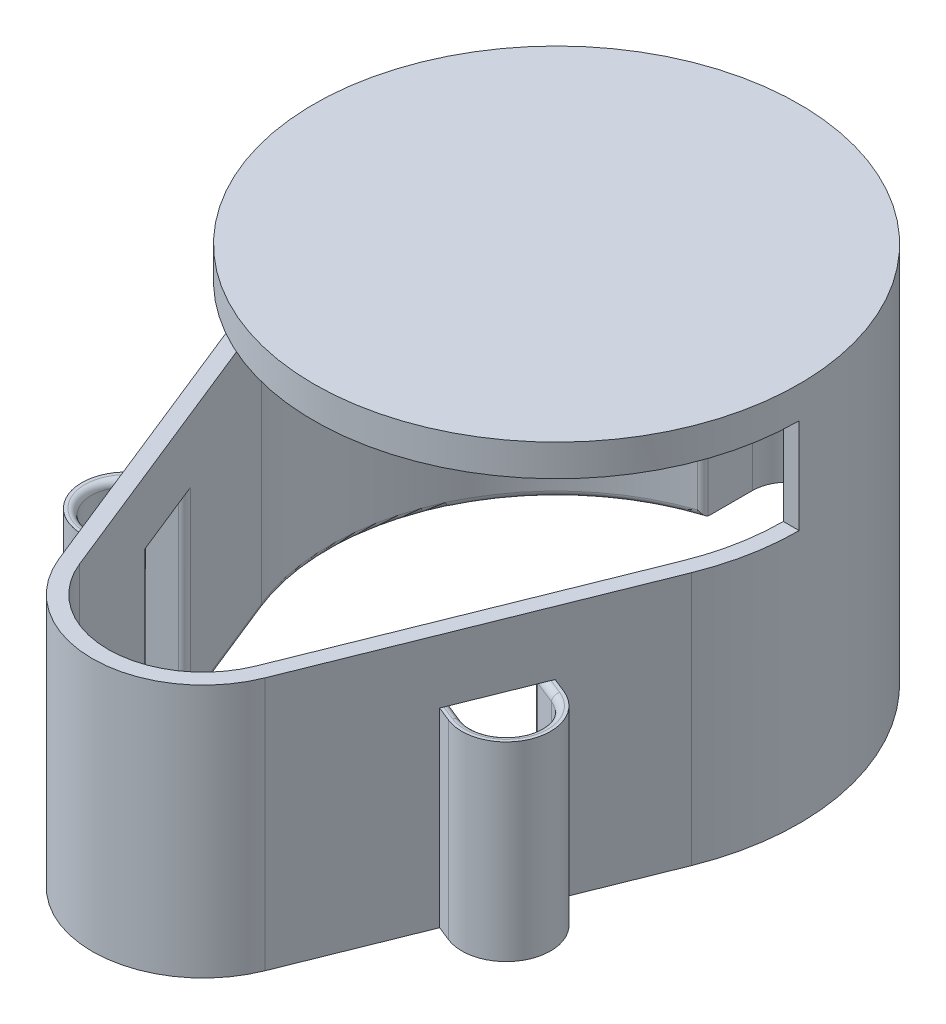
SolidWorks part; units mm, degrees
ref_plane "Front Plane" through (0, 0, 0) normal (0, 0, 1) x (1, 0, 0)
ref_plane "Top Plane" through (0, 0, 0) normal (0, 1, 0) x (1, 0, 0)
ref_plane "Right Plane" through (0, 0, 0) normal (1, 0, 0) x (0, 0, -1)
sketch "Sketch1" plane through (0, 0, 0) normal (0, 1, 0) x (1, 0, 0)
  line L0 (0, 0) -> (0, -55.7) construction
  line L1 (-35.4967, -14.2493) -> (-16.2403, -62.2193)
  line L2 (35.4967, -14.2493) -> (16.2403, -62.2193)
  line L3 (-33.1767, -13.318) -> (-13.9203, -61.288)
  line L4 (33.1767, -13.318) -> (13.9203, -61.288)
  line L5 (-28.1413, -32.5725) -> (-30.4614, -33.5039)
  line L7 (-25.2459, -46.4961) -> (-22.9259, -45.5648)
  line L8 (-28.1413, -32.5725) -> (-22.9259, -45.5648)
  line L9 (-35.4967, -14.2493) -> (-28.1413, -32.5725)
  line L10 (-29.9026, -34.8959) -> (-27.5825, -33.9646)
  line L11 (-25.8047, -45.1041) -> (-23.4847, -44.1728)
  line L12 (-27.5825, -33.9646) -> (-25.2625, -33.0332)
  line L13 (-23.4847, -44.1728) -> (-21.1646, -43.2415)
  line L14 (-21.1646, -43.2415) -> (-25.2625, -33.0332)
  line L15 (-28.1413, -32.5725) -> (-27.5825, -33.9646)
  line L16 (-23.4847, -44.1728) -> (-22.9259, -45.5648)
  line L17 (28.7868, -30.9646) -> (31.1069, -31.8959)
  line L19 (27.009, -42.1041) -> (24.689, -41.1728)
  line L20 (24.689, -41.1728) -> (28.7868, -30.9646)
  line L21 (29.3456, -29.5725) -> (31.6657, -30.5039)
  line L23 (26.4502, -43.4961) -> (24.1302, -42.5648)
  line L24 (24.1302, -42.5648) -> (29.3456, -29.5725)
  line L25 (24.689, -41.1728) -> (22.3689, -40.2415)
  line L26 (29.3456, -29.5725) -> (27.0256, -28.6412)
  line L27 (24.1302, -42.5648) -> (21.8101, -41.6335)
  line L28 (28.7868, -30.9646) -> (26.4668, -30.0332)
  line L29 (0, 57.7745) -> (0, 7.8021) construction
  line L30 (1.6, 41.7833) -> (1.6, 38.2165)
  line L31 (-12.4, 41.7833) -> (-12.4, 36.1843)
  line L32 (-10.9, 36.664) -> (-10.9, 41.7833)
  line L33 (0.1, 38.2499) -> (0.1, 41.7833)
  line L34 (-10.9, 36.664) -> (-10.9, 34.0478)
  line L35 (0.1, 38.2499) -> (0.1, 35.7499)
  arc A0 (-1.0953, -38.2343) -> (1.0953, -38.2343) centre (0, 0) ccw
  arc A1 (1.0953, -38.2343) -> (-1.0953, -38.2343) centre (0, -55.7) ccw
  arc A2 (35.4967, -14.2493) -> (-35.4967, -14.2493) centre (0, 0) ccw
  arc A3 (-16.2403, -62.2193) -> (16.2403, -62.2193) centre (0, -55.7) ccw
  arc A4 (33.1767, -13.318) -> (-33.1767, -13.318) centre (0, 0) ccw
  arc A5 (-13.9203, -61.288) -> (13.9203, -61.288) centre (0, -55.7) ccw
  arc A6 (-30.4614, -33.5039) -> (-25.2459, -46.4961) centre (-27.8537, -40) ccw
  arc A7 (-29.9026, -34.8959) -> (-25.8047, -45.1041) centre (-27.8537, -40) ccw
  arc A8 (31.1069, -31.8959) -> (27.009, -42.1041) centre (29.0579, -37) cw
  arc A9 (31.6657, -30.5039) -> (26.4502, -43.4961) centre (29.0579, -37) cw
  arc A10 (-12.4, 41.7833) -> (1.6, 41.7833) centre (-5.4, 41.7833) cw
  arc A11 (0.1, 41.7833) -> (-10.9, 41.7833) centre (-5.4, 41.7833) ccw
  dimension "D1" = 35
  dimension "D2" = 76.5
  dimension "D4" = 71.5
  dimension "D5" = 30
  dimension "D7" = 11
  dimension "D8" = 7
  dimension "D6" = 5.5
  dimension "D9" = 7
  dimension "D14" = 5.4
  dimension "D15" = 7
  dimension "D16" = 11
  dimension "D3" = 55.7
  dimension "D10" = 0
  dimension "D11" = 2.5
  dimension "D12" = 37
  dimension "D13" = 2.5
extrude "Boss-Extrude1" add sketch "Sketch1" along normal blind 30 contours A4 A2 L1 L12 L3 | A4 L4 L26 L2 A2 L35 | A11 L33 A2 L30 A10 L31 L32 | A7 L10 L1 L5 A6 L7 L11 | A5 L3 L13 L1 A3 L2 L27 L4 | A9 L21 L2 L17 A8 L19 L23 | L27 L2 L25 L4 | L28 L2 L26 L4 region at (-34.088, 0, -15.6111) region at (-28.0357, 0, 33.3383) region at (-12.2117, 0, -38.9838) region at (-22.1118, 0, 44.2373) region at (0.8329, 0, -37.4626) region at (30.4359, 0, 30.2119) region at (27.9062, 0, 29.8029) region at (23.2495, 0, 41.4031)
fillet "Fillet3" radius 1 18 edges at (28.7868, 30, 30.9646) (26.4668, 15, 30.0332) (22.3689, 15, 40.2415) (24.689, 30, 41.1728) (18.1446, 0, 50.7647) (-17.5425, 0, 52.2647) (-21.1646, 15, 43.2415) (-23.4847, 30, 44.1728) (-25.2625, 15, 33.0332) (-27.5825, 30, 33.9646) (-29.2196, 0, 23.1756) (-32.3507, 0, -15.2149) (-10.9, 15, -34.0478) (-10.9, 30, -37.9156) (0.1, 15, -35.7499) (0.1, 30, -38.7666) (29.6437, 0, -19.9828) (29.8217, 0, 21.6756) type face fillet first side face at (23.141, 15, -15.5994) first side face at (-27.1945, 15, -12.7899) first side face at (-17.5425, 15, 52.2647) first side face at (29.8217, 15, 21.6756) first side face at (-29.2196, 15, 23.1756) first side face at (18.1446, 15, 50.7647) first side face at (-0.8806, 30, 18.1744) second side face at (0.1, 15, -38.7666) second side face at (-10.9, 15, -37.9156) second side face at (-27.5825, 15, 33.9646) second side face at (-23.4847, 15, 44.1728) second side face at (28.7868, 15, 30.9646) second side face at (-0.8806, 0, 18.1744) second side face at (24.689, 15, 41.1728)
sketch "Sketch3" plane through (0, 30, 0) normal (0, 1, 0) x (1, 0, 0)
  line L0 (-35.4967, -14.2493) -> (-16.2403, -62.2193)
  line L1 (-33.1767, -13.318) -> (-13.9203, -61.288)
  line L2 (35.4967, -14.2493) -> (16.2403, -62.2193)
  line L3 (33.1767, -13.318) -> (13.9203, -61.288)
  arc A0 (33.1767, -13.318) -> (-33.1767, -13.318) centre (0, 0) ccw
  arc A1 (35.4967, -14.2493) -> (-35.4967, -14.2493) centre (0, 0) ccw
  arc A2 (-13.9203, -61.288) -> (13.9203, -61.288) centre (0, -55.7) ccw
  arc A3 (16.2403, -62.2193) -> (-16.2403, -62.2193) centre (0, -55.7) cw
extrude "Boss-Extrude2" add sketch "Sketch3" along normal blind 10
sketch "Sketch4" plane through (0, 40, 0) normal (0, 1, 0) x (1, 0, 0)
  line L0 (-38.25, 0) -> (38.25, 0)
  arc A0 (35.75, 0) -> (-35.75, 0) centre (0, 0) ccw
  arc A1 (38.25, 0) -> (-38.25, 0) centre (0, 0) ccw
  arc M4 (35.4967, -14.2493) -> (-35.4967, -14.2493) centre (0, 0) ccw
  arc M9 (-33.1767, -13.318) -> (33.1767, -13.318) centre (0, 0) cw
extrude "Boss-Extrude3" add sketch "Sketch4" along normal blind 15 contours L0 M4 M9 region at (0, 40, -37.3947)
sketch "Sketch5" plane through (0, 55, 0) normal (0, 1, 0) x (1, 0, 0)
  circle A1 centre (0, 0) radius 38.25
extrude "Boss-Extrude4" add sketch "Sketch5" along normal blind 5
